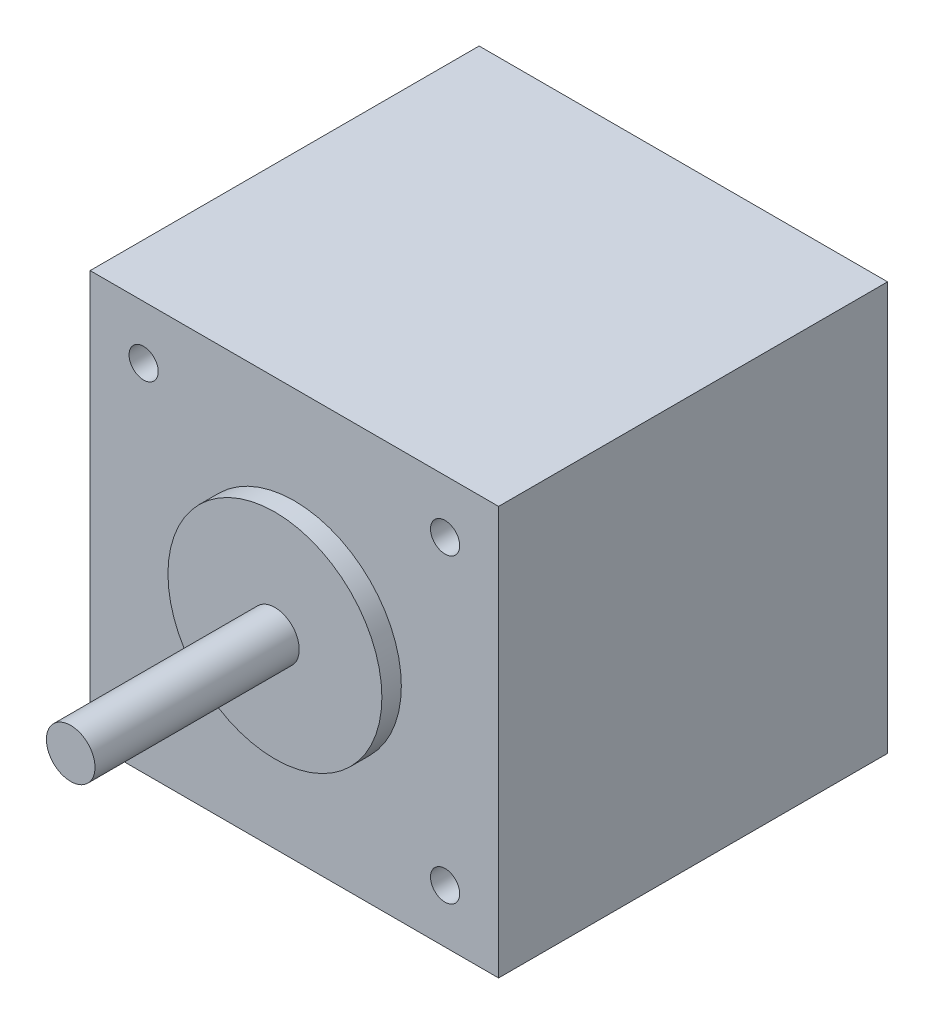
SolidWorks part; units mm, degrees
ref_plane "Спереди" through (0, 0, 0) normal (0, 0, 1) x (1, 0, 0)
ref_plane "Сверху" through (0, 0, 0) normal (0, 1, 0) x (1, 0, 0)
ref_plane "Справа" through (0, 0, 0) normal (1, 0, 0) x (0, 0, -1)
other "Configuration Table"
sketch "Эскиз1" plane through (0, 0, 0) normal (0, 0, 1) x (1, 0, 0)
  line L1 (-21, -21) -> (21, -21)
  line L2 (-21, -21) -> (-21, 21)
  line L3 (-21, 21) -> (21, 21)
  line L4 (21, -21) -> (21, 21)
  line L5 (-21, -21) -> (21, 21) construction
  line L6 (-21, 21) -> (21, -21) construction
  point P0 (0, 0)
  dimension "D1" = 42
  dimension "D2" = 42
extrude "Корпус" add sketch "Эскиз1" along normal blind 40
sketch "Эскиз2" plane through (0, 0, 0) normal (0, 0, 1) x (1, 0, 0)
  circle A0 centre (0, 0) radius 2.5
extrude "Вал_ПРЕДВ" add sketch "Эскиз2" along normal blind 63
sketch "Эскиз3" plane through (0, 0, 0) normal (0, 0, 1) x (1, 0, 0)
  circle A0 centre (0, 0) radius 11
  dimension "D1" = 22
extrude "Буртик_ПРЕДВ" add sketch "Эскиз3" along normal blind 42
sketch "Эскиз4" plane through (0, 0, 0) normal (0, 0, 1) x (1, 0, 0)
  circle A0 centre (-15.5, -15.5) radius 1.5
  circle A1 centre (-15.5, 15.5) radius 1.5
  circle A2 centre (15.5, -15.5) radius 1.5
  circle A3 centre (15.5, 15.5) radius 1.5
  dimension "D1" = 3
  dimension "D2" = 3
  dimension "D3" = 3
  dimension "D4" = 3
extrude "Крепеж_М3_ПРЕДВ" cut sketch "Эскиз4" against normal blind 4.5 from offset 40
equation "\"Мотор X ширина корпуса\"= 42.3"
equation "\"Мотор X высота корпуса\"= 42.3"
equation "\"Мотор X длина корпуса\"= 40"
equation "\"Мотор X вылет вала\"= 19.8"
equation "\"Мотор Y ширина корпуса\"= 42.3"
equation "\"Мотор Y высота корпуса\"= 42.3"
equation "\"Мотор Y длина корпуса\"= 48"
equation "\"Мотор Y вылет вала\"= 30"
equation "\"Мотор Z ширина корпуса\"= 42"
equation "\"Мотор Z высота корпуса\"= 42"
equation "\"Мотор Z длина корпуса\"= 40"
equation "\"Мотор Z вылет вала\"= 23"
equation "\"Мотор диаметр вала ПРЕДВ\"= 5"
equation "\"Мотор шаг крепления ПРЕДВ\"= 31"
equation "\"Мотор диаметр отверстий ПРЕДВ\"= 3"
equation "\"Мотор глубина отверстий ПРЕДВ\"= 4.5"
equation "\"Мотор диаметр буртика ПРЕДВ\"= 22"
equation "\"Мотор высота буртика ПРЕДВ\"= 2"
equation "\"Мотор диаметр шкива ПРЕДВ\"= 16"
equation "\"Мотор длина шкива ПРЕДВ\"= 12"
equation "\"Мотор отступ шкива ПРЕДВ\"= 5"
equation "\"Мотор X шаг градусов\"= 1.8"
equation "\"Мотор X ток А\"= 1.5"
equation "\"Мотор X сопротивление Ом\"= 1.3"
equation "\"Мотор X индуктивность мГн\"= 2"
equation "\"Мотор Y шаг градусов\"= 1.8"
equation "\"Мотор Y ток А\"= 2.2"
equation "\"Мотор Y сопротивление Ом\"= 0.9"
equation "\"Мотор Y индуктивность мГн\"= 2"
equation "\"Мотор Z шаг градусов\"= 1.8"
equation "\"Мотор Z ток А\"= 1"
equation "\"Мотор Z сопротивление Ом\"= 4"
equation "\"Мотор Z индуктивность мГн\"= 8"
equation "\"Мотор Y диаметр ротора\"= 25.78"
equation "\"D1@Эскиз1\" = \"Мотор Z ширина корпуса\""
equation "\"D2@Эскиз1\" = \"Мотор Z высота корпуса\""
equation "\"D1@Корпус\" = \"Мотор Z длина корпуса\""
equation "\"D1@Эскиз2\" = \"Мотор диаметр вала ПРЕДВ\""
equation "\"D1@Вал_ПРЕДВ\" = \"Мотор Z длина корпуса\" + \"Мотор Z вылет вала\""
equation "\"D1@Эскиз3\" = \"Мотор диаметр буртика ПРЕДВ\""
equation "\"D1@Буртик_ПРЕДВ\" = \"Мотор Z длина корпуса\" + \"Мотор высота буртика ПРЕДВ\""
equation "\"D1@Эскиз4\" = \"Мотор диаметр отверстий ПРЕДВ\""
equation "\"D2@Эскиз4\" = \"Мотор диаметр отверстий ПРЕДВ\""
equation "\"D3@Эскиз4\" = \"Мотор диаметр отверстий ПРЕДВ\""
equation "\"D4@Эскиз4\" = \"Мотор диаметр отверстий ПРЕДВ\""
equation "\"D1@Крепеж_М3_ПРЕДВ\" = \"Мотор глубина отверстий ПРЕДВ\""
equation "\"D19@Крепеж_М3_ПРЕДВ\" = \"Мотор Z длина корпуса\""
equation "\"Ширина груза\"= 420"
equation "\"Глубина груза\"= 490"
equation "\"Высота груза\"= 297"
equation "\"Ширина ячейки\"= \"Ширина груза\" + 10"
equation "\"Глубина ячейки\"= \"Глубина груза\" + 10"
equation "\"Высота ячейки\"= \"Высота груза\" + 10 + 13"
equation "\"Колво ячеек ширина\"= 2"
equation "\"Колво ячеек высота\"= 2"
equation "\"Толщина стенки\" = 6"
equation "\"Крепление дверцы\"= 5"
equation "\"Ширина рейки\"= \"Толщина шестерни\""
equation "\"Высота рейки\"= 20"
equation "\"Высота пола\"= 20"
equation "\"Колво полозьев\"= 5"
equation "\"Отступ рейки\"= 20"
equation "\"Глубина каретки\"= \"Глубина ячейки\" + 30 + \"Мотор Y высота корпуса\" + 20"
equation "\"Отступ шпильки\"= 26"
equation "\"Диаметр шпильки\"= 5"
equation "\"Длинна шпильки\"= ( \"Высота ячейки\" + \"Толщина стенки\" + \"Высота пола\" ) * \"Колво ячеек высота\" + ( \"Толщина стенки\" + \"Отступ рейки\" ) * 2 "
equation "\"Ширина пластины\"= 50  "
equation "\"Высота зона выгрузки\"= \"Высота ячейки\" * 2 + \"Толщина стенки\" * 2"
equation "\"Колво выгрузки\"= 1"
equation "\"Отступ крепления мотора фиксации\" = 30"
equation "\"Диаметр оси\"= 10"
equation "\"Диаметр ролика\"= 20"
equation "\"Колво роликов\"= 10"
equation "\"Шаг роликов\"= \"Диаметр ролика\" + 20"
equation "\"Ширина ячейки выгрузки\"= \"Ширина ячейки\" + \"Толщина стенки\" + \"Отступ крепления мотора фиксации\"*2"
equation "\"Длинна рейки\"= ( \"Ширина ячейки\" + \"Толщина стенки\" + \"Крепление дверцы\" ) * \"Колво ячеек ширина\" + \"Ширина ячейки выгрузки\" * \"Колво выгрузки\" + \"Толщина стенки\""
